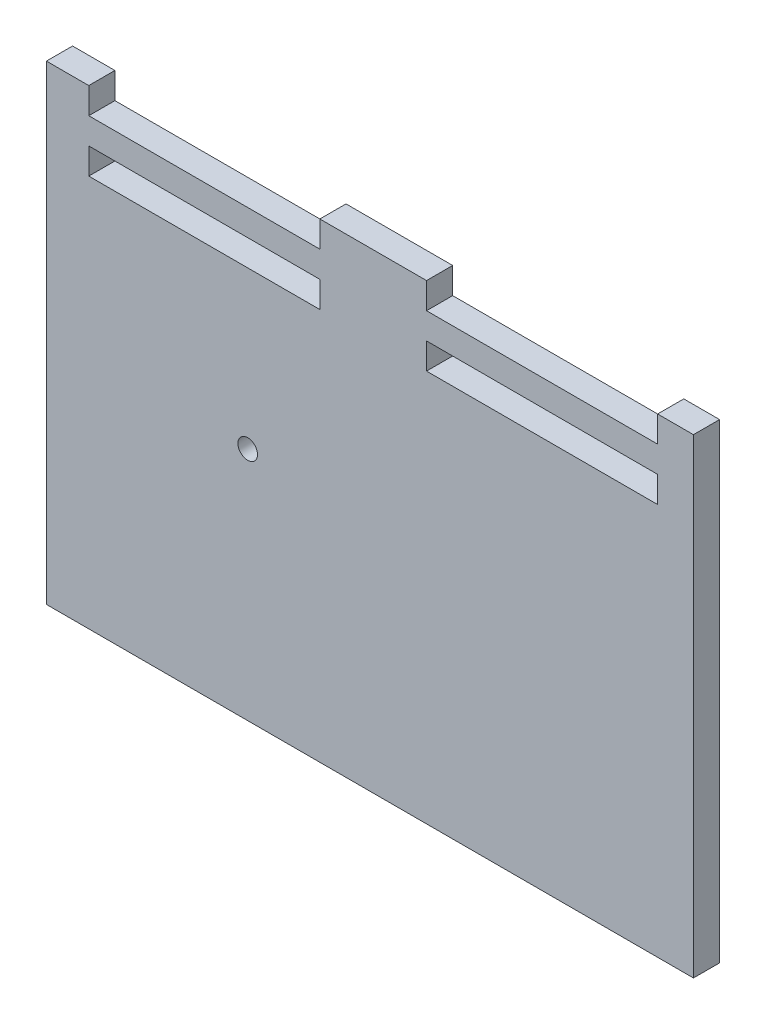
SolidWorks part; units mm, degrees
ref_plane "Front Plane" through (0, 0, 0) normal (0, 0, 1) x (1, 0, 0)
ref_plane "Top Plane" through (0, 0, 0) normal (0, 1, 0) x (1, 0, 0)
ref_plane "Right Plane" through (0, 0, 0) normal (1, 0, 0) x (0, 0, -1)
sketch "Sketch1" plane through (0, 0, 0) normal (0, 0, 1) x (1, 0, 0)
  line L1 (0, 0) -> (304.8, 0)
  line L2 (0, 0) -> (0, 228.6)
  line L3 (0, 228.6) -> (304.8, 228.6)
  line L4 (304.8, 0) -> (304.8, 228.6)
  dimension "D1" = 304.8
  dimension "D2" = 228.6
extrude "Boss-Extrude1" add sketch "Sketch1" along normal blind 12.7
sketch "Sketch2" plane through (0, 0, 12.7) normal (0, 0, 1) x (1, 0, 0)
  line L0 (304.8, 228.6) -> (0, 228.6) construction
  line L1 (0, 228.6) -> (0, 0) construction
  circle A0 centre (91.44, 114.3) radius 4.7625
  dimension "D1" = 9.525
  dimension "D2" = 114.3
  dimension "D3" = 91.44
extrude "Cut-Extrude1" cut sketch "Sketch2" against normal blind 12.7
sketch "Sketch6" plane through (0, 0, 12.7) normal (0, 0, 1) x (1, 0, 0)
  line L0 (0, 114.3) -> (304.8, 114.3) construction
  line L1 (0, 228.6) -> (0, 0) construction
  line L2 (304.8, 0) -> (304.8, 228.6) construction
sketch "Sketch7" plane through (0, 0, 12.7) normal (0, 0, 1) x (1, 0, 0)
  line L1 (14.224, 228.6) -> (126.492, 228.6)
  line L2 (14.224, 228.6) -> (14.224, 215.9)
  line L3 (14.224, 215.9) -> (126.492, 215.9)
  line L4 (0, 228.6) -> (0, 0)
  line L5 (0, 0) -> (304.8, 0)
  line L6 (304.8, 0) -> (304.8, 228.6)
  line L7 (304.8, 228.6) -> (0, 228.6)
  line L8 (0, 228.6) -> (0, 0)
  line L9 (0, 0) -> (304.8, 0)
  line L10 (304.8, 0) -> (304.8, 228.6)
  line L11 (304.8, 228.6) -> (0, 228.6)
  line L12 (126.492, 228.6) -> (126.492, 215.9)
  line L13 (178.308, 228.6) -> (290.576, 228.6)
  line L14 (178.308, 228.6) -> (178.308, 215.9)
  line L15 (178.308, 215.9) -> (290.576, 215.9)
  line L16 (290.576, 228.6) -> (290.576, 215.9)
  line L17 (14.224, 203.2) -> (126.492, 203.2)
  line L18 (14.224, 203.2) -> (14.224, 190.5)
  line L19 (14.224, 190.5) -> (126.492, 190.5)
  line L20 (126.492, 203.2) -> (126.492, 190.5)
  line L21 (178.308, 203.2) -> (290.576, 203.2)
  line L22 (178.308, 203.2) -> (178.308, 190.5)
  line L23 (178.308, 190.5) -> (290.576, 190.5)
  line L24 (290.576, 203.2) -> (290.576, 190.5)
  point P20 (70.358, 203.2)
  line M17 (304.8, 228.6) -> (0, 228.6)
  dimension "D2" = 14.224
  dimension "D3" = 112.268
  dimension "D4" = 112.268
  dimension "D5" = 14.224
  dimension "D6" = 12.7
  dimension "D7" = 12.7
  dimension "D8" = 12.7
  dimension "D9" = 112.268
  dimension "D10" = 112.268
  dimension "D11" = 12.7
  dimension "D12" = 12.7
  dimension "D1" = 0
extrude "Cut-Extrude2" cut sketch "Sketch7" against normal blind 12.7 contours L12 L2 L3 M17 | L15 L16 L13 L14 | L18 L17 L20 L19 | L22 L21 L24 L23 region at (70.358, 222.25, 12.7)
sketch "Sketch8" plane through (0, 0, 12.7) normal (0, 0, 1) x (1, 0, 0)
  line L1 (304.8, 228.6) -> (307.975, 228.6)
  line L2 (304.8, 228.6) -> (304.8, 0)
  line L3 (304.8, 0) -> (307.975, 0)
  line L4 (307.975, 228.6) -> (307.975, 0)
  line L5 (0, 228.6) -> (-6.35, 228.6)
  line L6 (0, 228.6) -> (0, 0)
  line L7 (0, 0) -> (-6.35, 0)
  line L8 (-6.35, 228.6) -> (-6.35, 0)
  line L12 (290.576, 215.9) -> (178.308, 215.9)
  line L13 (178.308, 215.9) -> (178.308, 228.6)
  line L14 (178.308, 228.6) -> (126.492, 228.6)
  line L15 (126.492, 228.6) -> (126.492, 215.9)
  line L16 (126.492, 215.9) -> (14.224, 215.9)
  line L17 (14.224, 215.9) -> (14.224, 228.6)
  line L18 (14.224, 228.6) -> (0, 228.6)
  line L19 (0, 228.6) -> (0, 0)
  line L20 (0, 0) -> (304.8, 0)
  line L21 (304.8, 0) -> (304.8, 228.6)
  line L22 (304.8, 228.6) -> (290.576, 228.6)
  line L23 (290.576, 228.6) -> (290.576, 215.9)
  line L24 (290.576, 215.9) -> (178.308, 215.9)
  line L25 (178.308, 215.9) -> (178.308, 228.6)
  line L26 (178.308, 228.6) -> (126.492, 228.6)
  line L27 (126.492, 228.6) -> (126.492, 215.9)
  line L28 (126.492, 215.9) -> (14.224, 215.9)
  line L29 (14.224, 215.9) -> (14.224, 228.6)
  line L30 (14.224, 228.6) -> (0, 228.6)
  line L31 (0, 228.6) -> (0, 0)
  line L32 (0, 0) -> (304.8, 0)
  line L33 (304.8, 0) -> (304.8, 228.6)
  line L34 (304.8, 228.6) -> (290.576, 228.6)
  line L35 (290.576, 228.6) -> (290.576, 215.9)
  line M22 (0, 228.6) -> (0, 0)
  line M24 (304.8, 0) -> (304.8, 228.6)
  dimension "D2" = 6.35
  dimension "D3" = 3.175
  dimension "D1" = 0
extrude "Boss-Extrude2" add sketch "Sketch8" against normal blind 12.7 contours L5 L8 L7 M22 | L4 L1 L3 M24 region at (306.3875, 114.3, 12.7) region at (-3.175, 114.3, 12.7)
